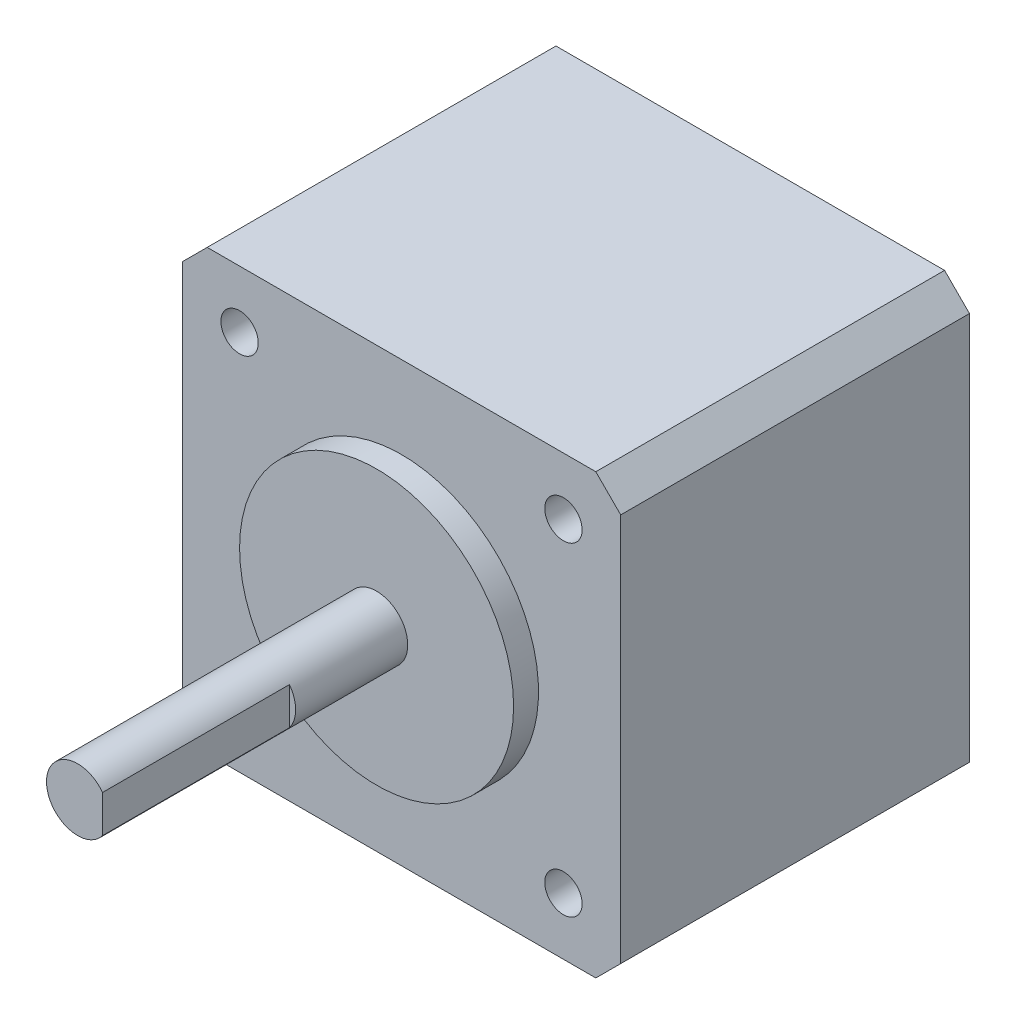
SolidWorks part; units mm, degrees
ref_plane "Plan de face" through (0, 0, 0) normal (0, 0, 1) x (1, 0, 0)
ref_plane "Plan de dessus" through (0, 0, 0) normal (0, 1, 0) x (1, 0, 0)
ref_plane "Plan de droite" through (0, 0, 0) normal (1, 0, 0) x (0, 0, -1)
sketch "Esquisse2" plane through (0, 0, 0) normal (0, 0, 1) x (1, 0, 0)
  line L1 (0, 0) -> (35.2, 0)
  line L2 (0, 0) -> (0, 35.2)
  line L3 (0, 35.2) -> (35.2, 35.2)
  line L4 (35.2, 0) -> (35.2, 35.2)
  dimension "D2" = 35.2
extrude "Boss.-Extru.1" add sketch "Esquisse2" along normal blind 28
sketch "Esquisse3" plane through (0, 0, 28) normal (0, 0, 1) x (1, 0, 0)
  line L0 (35.2, 17.6) -> (0, 17.6) construction
  line L1 (35.2, 0) -> (35.2, 35.2) construction
  line L2 (0, 35.2) -> (0, 0) construction
  circle A0 centre (17.6, 17.6) radius 11
  dimension "D1" = 22
extrude "Boss.-Extru.2" add sketch "Esquisse3" along normal blind 2
sketch "Esquisse4" plane through (0, 0, 30) normal (0, 0, 1) x (1, 0, 0)
  circle A0 centre (17.6, 17.6) radius 2.5
  circle A1 centre (17.6, 17.6) radius 11 construction
  dimension "D1" = 5
extrude "Boss.-Extru.3" add sketch "Esquisse4" along normal blind 24
sketch "Esquisse5" plane through (0, 0, 54) normal (0, 0, 1) x (1, 0, 0)
  line L0 (19.6, 19.1) -> (19.6, 16.1)
  line L1 (15.1, 19.8092) -> (15.1, 15.6143) construction
  circle A0 centre (17.6, 17.6) radius 2.5 construction
  arc A1 (19.6, 16.1) -> (19.6, 19.1) centre (17.6, 17.6) ccw
  dimension "D1" = 4.5
extrude "Enlèv. mat.-Extru.1" cut sketch "Esquisse5" against normal blind 15
chamfer "Chanfrein1" distance 2 angle 45 4 edges at (0, 0, 14) (35.2, 0, 14) (0, 35.2, 14) (35.2, 35.2, 14)
sketch "Esquisse6" plane through (0, 0, 28) normal (0, 0, 1) x (1, 0, 0)
  line L0 (35.2, 17.6) -> (0, 17.6) construction
  line L1 (35.2, 2) -> (35.2, 33.2) construction
  line L2 (0, 33.2) -> (0, 2) construction
  line L3 (17.6, 0) -> (17.6, 35.2) construction
  line L4 (2, 0) -> (33.2, 0) construction
  line L5 (33.2, 35.2) -> (2, 35.2) construction
  line L6 (34.2, 34.2) -> (17.6, 17.6) construction
  line L7 (35.2, 33.2) -> (33.2, 35.2) construction
  circle A0 centre (30.6, 30.6) radius 1.5
  circle A1 centre (30.6, 4.6) radius 1.5
  circle A2 centre (4.6, 4.6) radius 1.5
  circle A3 centre (4.6, 30.6) radius 1.5
  dimension "D2" = 3
  dimension "D1" = 26
extrude "Enlèv. mat.-Extru.2" cut sketch "Esquisse6" against normal blind 4.5
ref_axis "Axe1" through (35.2, 17.6, 36.2426) along (0, 0, -1)
